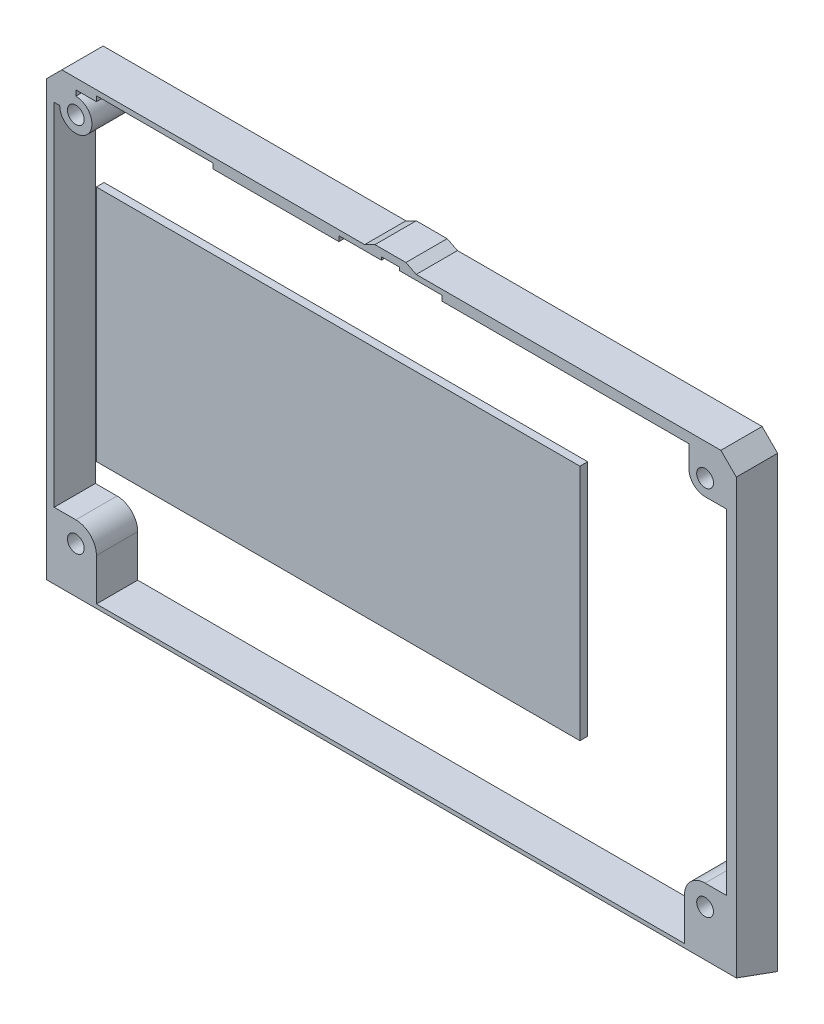
SolidWorks part; units mm, degrees
ref_plane "Front Plane" through (0, 0, 0) normal (0, 0, 1) x (1, 0, 0)
ref_plane "Top Plane" through (0, 0, 0) normal (0, 1, 0) x (1, 0, 0)
ref_plane "Right Plane" through (0, 0, 0) normal (1, 0, 0) x (0, 0, -1)
sketch "Sketch1" plane through (0, 0, 0) normal (0, 0, 1) x (1, 0, 0)
  line L0 (-64.55, -48.1345) -> (64.9102, -48.1345)
  line L1 (-57, 40.2) -> (-61, 40.2)
  line L2 (-65.2, 32) -> (-65.2, 36)
  line L3 (-64.125, 36) -> (-65.2, 36)
  line L4 (-61, 39.125) -> (-61, 40.2)
  line L5 (-57, 40.2) -> (-57, 41.2)
  line L6 (-57, 41.2) -> (-34.381, 41.2)
  line L7 (-34.381, 41.2) -> (-34.381, 40.2)
  line L8 (-34.381, 34.97) -> (-34.381, 29.87) construction
  line L9 (-34.381, 34.97) -> (-34.381, 29.87)
  line L10 (57.875, 36) -> (57.875, 40.2)
  line L11 (-10, 40.2) -> (10, 40.2)
  line L12 (-10, 40.2) -> (-10, 41.2)
  line L13 (-10, 41.2) -> (10, 41.2)
  line L14 (10, 40.2) -> (10, 41.2)
  line L15 (57.875, 40.2) -> (57, 40.2)
  line L16 (61, 32.875) -> (65.2, 32.875)
  line L17 (65.2, 32.875) -> (65.2, 32)
  line L18 (-2.4398, -40.2) -> (2.5602, -40.2)
  line L19 (-57, -40.2) -> (-57, -44.1345)
  line L20 (-66.7, -48.1345) -> (67.0602, -48.1345)
  line L21 (-66.7, -48.1345) -> (-66.7, -44.1345)
  line L22 (-66.7, -44.1345) -> (67.0602, -44.1345)
  line L23 (67.0602, -48.1345) -> (67.0602, -44.1345)
  line L24 (57, -40.2) -> (57, -44.1345)
  line L56 (-2.4398, -52.9233) -> (-2.4398, -40.2)
  line L57 (-2.4398, -40.2) -> (-6.5, -40.2)
  line L58 (-6.5, -40.2) -> (-6.5, -43.2)
  line L59 (-6.5, -43.2) -> (-25.5, -43.2)
  line L60 (-25.5, -43.2) -> (-25.5, -40.2)
  line L61 (-25.5, -40.2) -> (-57, -40.2)
  line L62 (-57, -40.2) -> (-57, -36)
  line L63 (-61, -32) -> (-65.2, -32)
  line L64 (-65.2, -32) -> (-65.2, 32)
  line L65 (-65.2, 32) -> (-61, 32)
  line L66 (-57, 36) -> (-57, 40.2)
  line L67 (-57, 40.2) -> (-10, 40.2)
  line L68 (-10, 40.2) -> (-10, 40.7)
  line L69 (-10, 40.7) -> (-1.75, 40.7)
  line L70 (-1.75, 40.7) -> (-1.75, 41.8)
  line L71 (-1.75, 41.8) -> (1.75, 41.8)
  line L72 (1.75, 41.8) -> (1.75, 40.7)
  line L73 (1.75, 40.7) -> (10, 40.7)
  line L74 (10, 40.7) -> (10, 40.2)
  line L75 (10, 40.2) -> (57, 40.2)
  line L76 (57, 40.2) -> (57, 36)
  line L77 (61, 32) -> (65.2, 32)
  line L78 (65.2, 32) -> (65.2, -32)
  line L79 (65.2, -32) -> (61, -32)
  line L80 (57, -36) -> (57, -40.2)
  line L81 (57, -40.2) -> (2.5602, -40.2)
  line L82 (2.5602, -40.2) -> (2.5602, -48.1345)
  line L83 (2.5602, -48.1345) -> (35.5602, -48.1345)
  line L84 (35.5602, -48.1345) -> (35.5602, -52.9233)
  line L85 (35.5602, -52.9233) -> (53.0602, -52.9233)
  line L86 (53.0602, -52.9233) -> (53.0602, -48.1345)
  line L87 (53.0602, -48.1345) -> (61.9102, -48.1345)
  line L88 (61.9102, -48.1345) -> (61.9102, -66.2255)
  line L89 (61.9102, -66.2255) -> (64.9102, -66.2255)
  line L90 (64.9102, -66.2255) -> (64.9102, -48.1345)
  line L91 (64.9102, -48.1345) -> (67.0602, -48.1345)
  line L92 (67.0602, -48.1345) -> (67.0602, 39.2)
  line L93 (67.0602, 39.2) -> (64.0602, 42.2)
  line L94 (64.0602, 42.2) -> (5, 42.2)
  line L95 (5, 42.2) -> (3, 43.2)
  line L96 (3, 43.2) -> (-3, 43.2)
  line L97 (-3, 43.2) -> (-5, 42.2)
  line L98 (-5, 42.2) -> (-63.7, 42.2)
  line L99 (-63.7, 42.2) -> (-66.7, 39.2)
  line L100 (-66.7, 39.2) -> (-66.7, -48.1345)
  line L101 (-66.7, -48.1345) -> (-64.55, -48.1345)
  line L102 (-64.55, -48.1345) -> (-64.55, -66.2255)
  line L103 (-64.55, -66.2255) -> (-61.55, -66.2255)
  line L104 (-61.55, -66.2255) -> (-61.55, -48.1345)
  line L105 (-61.55, -48.1345) -> (-52.7, -48.1345)
  line L106 (-52.7, -48.1345) -> (-52.7, -52.9233)
  line L107 (-52.7, -52.9233) -> (-41.2, -52.9233)
  line L108 (-41.2, -52.9233) -> (-41.2, -48.1345)
  line L109 (-41.2, -48.1345) -> (-13.9398, -48.1345)
  line L110 (-13.9398, -48.1345) -> (-13.9398, -52.9233)
  line L111 (-13.9398, -52.9233) -> (-2.4398, -52.9233)
  line L112 (-2.4398, -52.9233) -> (-2.4398, -40.2)
  line L113 (-2.4398, -40.2) -> (-6.5, -40.2)
  line L114 (-6.5, -40.2) -> (-6.5, -43.2)
  line L115 (-6.5, -43.2) -> (-25.5, -43.2)
  line L116 (-25.5, -43.2) -> (-25.5, -40.2)
  line L117 (-25.5, -40.2) -> (-57, -40.2)
  line L118 (-57, -40.2) -> (-57, -36)
  line L119 (-61, -32) -> (-65.2, -32)
  line L120 (-65.2, -32) -> (-65.2, 32)
  line L121 (-65.2, 32) -> (-61, 32)
  line L122 (-57, 36) -> (-57, 40.2)
  line L123 (-57, 40.2) -> (-10, 40.2)
  line L124 (-10, 40.2) -> (-10, 40.7)
  line L125 (-10, 40.7) -> (-1.75, 40.7)
  line L126 (-1.75, 40.7) -> (-1.75, 41.8)
  line L127 (-1.75, 41.8) -> (1.75, 41.8)
  line L128 (1.75, 41.8) -> (1.75, 40.7)
  line L129 (1.75, 40.7) -> (10, 40.7)
  line L130 (10, 40.7) -> (10, 40.2)
  line L131 (10, 40.2) -> (57, 40.2)
  line L132 (57, 40.2) -> (57, 36)
  line L133 (61, 32) -> (65.2, 32)
  line L134 (65.2, 32) -> (65.2, -32)
  line L135 (65.2, -32) -> (61, -32)
  line L136 (57, -36) -> (57, -40.2)
  line L137 (57, -40.2) -> (2.5602, -40.2)
  line L138 (2.5602, -40.2) -> (2.5602, -48.1345)
  line L139 (2.5602, -48.1345) -> (35.5602, -48.1345)
  line L140 (35.5602, -48.1345) -> (35.5602, -52.9233)
  line L141 (35.5602, -52.9233) -> (53.0602, -52.9233)
  line L142 (53.0602, -52.9233) -> (53.0602, -48.1345)
  line L143 (53.0602, -48.1345) -> (61.9102, -48.1345)
  line L144 (61.9102, -48.1345) -> (61.9102, -66.2255)
  line L145 (61.9102, -66.2255) -> (64.9102, -66.2255)
  line L146 (64.9102, -66.2255) -> (64.9102, -48.1345)
  line L147 (64.9102, -48.1345) -> (67.0602, -48.1345)
  line L148 (67.0602, -48.1345) -> (67.0602, 39.2)
  line L149 (67.0602, 39.2) -> (64.0602, 42.2)
  line L150 (64.0602, 42.2) -> (5, 42.2)
  line L151 (5, 42.2) -> (3, 43.2)
  line L152 (3, 43.2) -> (-3, 43.2)
  line L153 (-3, 43.2) -> (-5, 42.2)
  line L154 (-5, 42.2) -> (-63.7, 42.2)
  line L155 (-63.7, 42.2) -> (-66.7, 39.2)
  line L156 (-66.7, 39.2) -> (-66.7, -48.1345)
  line L157 (-66.7, -48.1345) -> (-64.55, -48.1345)
  line L158 (-64.55, -48.1345) -> (-64.55, -66.2255)
  line L159 (-64.55, -66.2255) -> (-61.55, -66.2255)
  line L160 (-61.55, -66.2255) -> (-61.55, -48.1345)
  line L161 (-61.55, -48.1345) -> (-52.7, -48.1345)
  line L162 (-52.7, -48.1345) -> (-52.7, -52.9233)
  line L163 (-52.7, -52.9233) -> (-41.2, -52.9233)
  line L164 (-41.2, -52.9233) -> (-41.2, -48.1345)
  line L165 (-41.2, -48.1345) -> (-13.9398, -48.1345)
  line L166 (-13.9398, -48.1345) -> (-13.9398, -52.9233)
  line L167 (-13.9398, -52.9233) -> (-2.4398, -52.9233)
  circle A0 centre (-61, 36) radius 1.625 construction
  circle A1 centre (-61, 36) radius 1.625
  circle A2 centre (-61, 36) radius 3.125
  circle A3 centre (61, 36) radius 1.625 construction
  arc A4 (-57, -36) -> (-61, -32) centre (-61, -36) ccw
  arc A5 (-61, 32) -> (-57, 36) centre (-61, 36) ccw
  arc A6 (57, 36) -> (61, 32) centre (61, 36) ccw
  arc A7 (61, -32) -> (57, -36) centre (61, -36) ccw
  arc A8 (-57, -36) -> (-61, -32) centre (-61, -36) ccw
  arc A9 (-61, 32) -> (-57, 36) centre (-61, 36) ccw
  arc A10 (57, 36) -> (61, 32) centre (61, 36) ccw
  arc A11 (61, -32) -> (57, -36) centre (61, -36) ccw
  circle A12 centre (61, 36) radius 1.625
  circle A13 centre (61, 36) radius 3.125
  circle A14 centre (61, -36) radius 1.625 construction
  circle A15 centre (61, -36) radius 1.625
  circle A16 centre (-61, -36) radius 1.625 construction
  circle A17 centre (-61, -36) radius 1.625
  dimension "D2" = 1.5
  dimension "D3" = 1
  dimension "D4" = 1.5
  dimension "D5" = 4
  dimension "D1" = 0
extrude "Boss-Extrude1" add sketch "Sketch1" along normal blind 8 contours A13 L16 L17 L134 L135 A11 L136 L24 L22 L148 L149 L150 L151 L152 L153 L154 L155 L156 L19 L118 A8 L119 L120 L2 L3 A2 L4 L1 L5 L6 L7 L123 L12 L13 L126 L127 L128 L14 L131 L15 L10 A17 A15 | L0 L20 L112 L22 L21 | L138 L22 L112 L20 | L22 L138 L0 L20 L23 | A2 A1 | A13 A12 region at (-34.5699, -46.1345, 0) region at (-66.5403, -2.4672, 0) region at (0.0602, -46.1345, 0) region at (34.8102, -46.1345, 0) region at (-63.1472, 38.1472, 0) region at (58.8528, 33.8528, 0)
sketch "Sketch2" plane through (-66.7, 0, 0) normal (-1, 0, 0) x (0, 0, 1)
  line L0 (0.4894, -47.6371) -> (26.1892, -38.2831)
  line L1 (26.1892, -38.2831) -> (27.8501, -42.8464)
  line L2 (27.8501, -42.8464) -> (-0.169, -53.0445)
  line L3 (-0.169, -53.0445) -> (-1.8299, -48.4812)
  line L4 (-1.8299, -48.4812) -> (0.4894, -47.6371)
  line L5 (-22.8114, -56.4371) -> (39.4671, -33.7696) construction
  dimension "D1" = 0.3
extrude "Cut-Extrude1" cut sketch "Sketch2" against normal through all
ref_plane "Plane1" through (0, 0, 16.8275) normal (0, 0, 1) x (1, 0, 0)
sketch "Sketch3" plane through (0, 0, 16.8275) normal (0, 0, 1) x (1, 0, 0)
  line L0 (-66.7, -2.8517) -> (67.0602, -2.8517) construction
  line L1 (-66.7, 39.2) -> (-66.7, -44.9035) construction
  line L2 (67.0602, -44.9035) -> (67.0602, 39.2) construction
  line L3 (0.1801, -2.8517) -> (0.1801, 47.0688) construction
  line L4 (64.0602, 42.2) -> (5, 42.2) construction
  line L5 (-46.7, -9.9035) -> (47.0602, -9.9035)
  line L6 (-46.7, -9.9035) -> (-46.7, 36.2)
  line L7 (-46.7, 36.2) -> (47.0602, 36.2)
  line L8 (47.0602, -9.9035) -> (47.0602, 36.2)
  line L9 (-46.7, -9.9035) -> (47.0602, 36.2) construction
  line L10 (-46.7, 36.2) -> (47.0602, -9.9035) construction
  line L11 (67.0602, -44.9035) -> (-66.7, -44.9035) construction
  point P8 (0.1801, 13.1483)
  dimension "D1" = 6
  dimension "D2" = 20
  dimension "D3" = 35
extrude "Boss-Extrude2" add sketch "Sketch3" along normal blind 1.5 separate body
